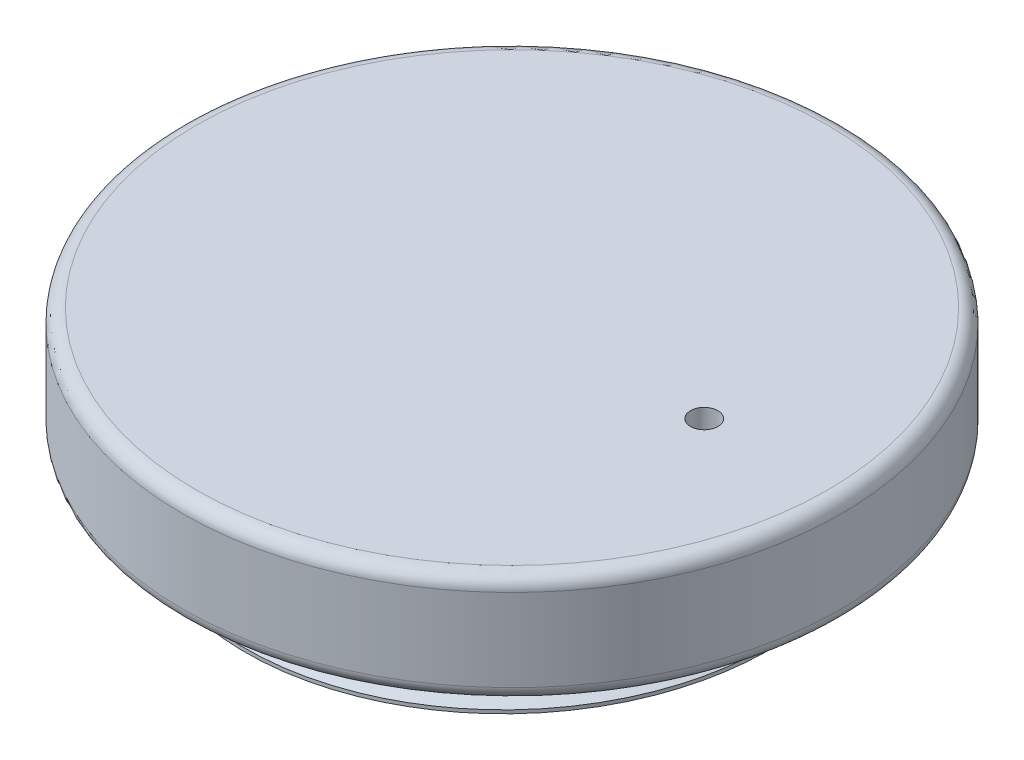
SolidWorks part; units mm, degrees
material "AISI 304"
ref_plane "Front Plane" through (0, 0, 0) normal (0, 0, 1) x (1, 0, 0)
ref_plane "Top Plane" through (0, 0, 0) normal (0, 1, 0) x (1, 0, 0)
ref_plane "Right Plane" through (0, 0, 0) normal (1, 0, 0) x (0, 0, -1)
sketch "Sketch1" plane through (0, 0, 0) normal (0, 1, 0) x (1, 0, 0)
  circle A0 centre (0, 0) radius 9
  dimension "D1" = 18
extrude "Boss-Extrude1" add sketch "Sketch1" along normal blind 2
sketch "Sketch2" plane through (0, 2, 0) normal (0, 1, 0) x (1, 0, 0)
  circle A0 centre (0, 0) radius 12
  dimension "D1" = 24
extrude "Boss-Extrude2" add sketch "Sketch2" along normal blind 4
thread "Thread1" pitch 1 method extrude profile "Thread Profile1" start angle 0, offset 0, length 0, pitch 1, diameter 18
ref_plane "Plane1" through (-9, 2, 0) normal (0, 0, 1) x (-1, 0, 0)
sketch "Thread Profile1" plane through (-9, 2, 0) normal (0, 0, 1) x (-1, 0, 0)
  line L0 (0, 0) -> (0, 1) construction
  line L1 (0, 0) -> (0.5413, 0.3125)
  line L2 (0.5413, 0.3125) -> (0.5413, 0.4375)
  line L3 (0.5413, 0.4375) -> (0, 0.75)
  line L4 (0.5413, 0.375) -> (0, 0.375) construction
  line L11 (0, 0) -> (0, 0.75)
  point P2 (0, 0)
  dimension "Pitch" = 1
  dimension "Profile_Angle" = 60
  dimension "Profile_Land" = 0.125
  dimension "Profile_Height" = 0.5413
fillet "Fillet1" radius 0.5 2 edges at (0, 6, 12) (0, 2, 12)
sketch "Sketch3" plane through (0, 6, 0) normal (0, 1, 0) x (1, 0, 0)
  circle A0 centre (7, 0) radius 0.5
  circle A1 centre (0, 0) radius 12 construction
  dimension "D1" = 1
  dimension "D2" = 7
extrude "Cut-Extrude1" cut sketch "Sketch3" against normal through all
